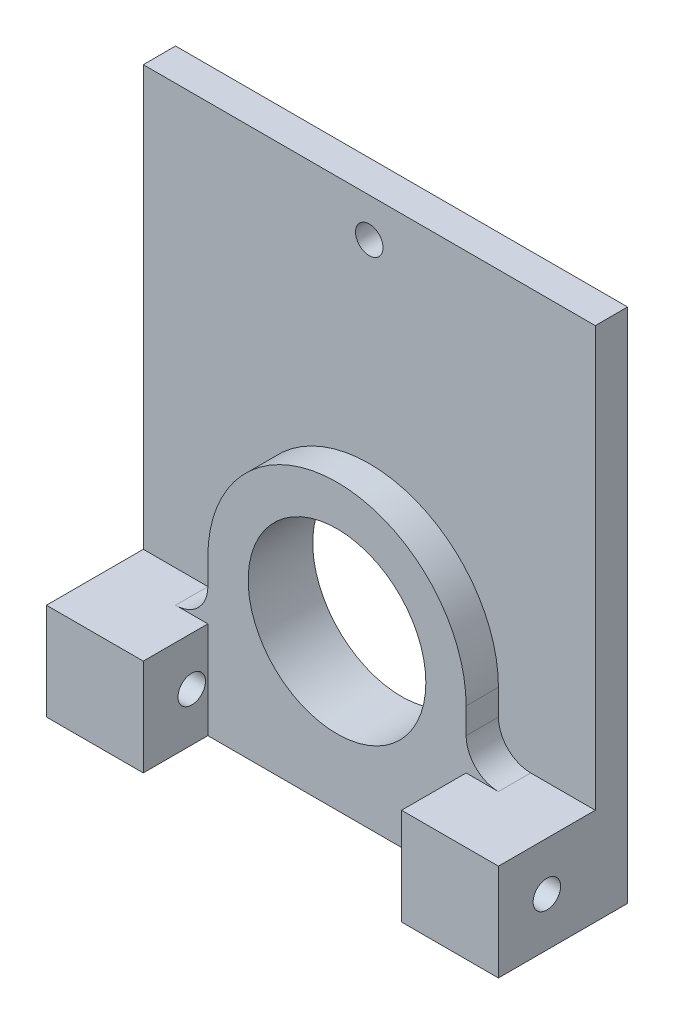
SolidWorks part; units mm, degrees
material "6061 Alloy"
ref_plane "Front Plane" through (0, 0, 0) normal (0, 0, 1) x (1, 0, 0)
ref_plane "Top Plane" through (0, 0, 0) normal (0, 1, 0) x (1, 0, 0)
ref_plane "Right Plane" through (0, 0, 0) normal (1, 0, 0) x (0, 0, -1)
sketch "Sketch1" plane through (0, 0, 0) normal (0, 0, 1) x (1, 0, 0)
  line L1 (-22.225, 25.4) -> (22.225, 25.4)
  line L2 (-22.225, 25.4) -> (-22.225, -25.4)
  line L3 (-22.225, -25.4) -> (22.225, -25.4)
  line L4 (22.225, 25.4) -> (22.225, -25.4)
  line L5 (-22.225, 25.4) -> (22.225, -25.4) construction
  line L6 (-22.225, -25.4) -> (22.225, 25.4) construction
  point P0 (0, 0)
  dimension "D1" = 44.45
  dimension "D2" = 50.8
extrude "Boss-Extrude1" add sketch "Sketch1" along normal blind 3.175
sketch "Sketch2" plane through (0, 0, 3.175) normal (0, 0, 1) x (1, 0, 0)
  line L0 (-12.7, -10.16) -> (-12.7, -25.4)
  line L1 (-22.225, -25.4) -> (22.225, -25.4) construction
  line L2 (12.7, -10.16) -> (12.7, -25.4)
  line L3 (-12.7, -25.4) -> (12.7, -25.4)
  arc A0 (12.7, -10.16) -> (-12.7, -10.16) centre (0, -10.16) ccw
  dimension "D1" = 25.4
  dimension "D2" = 15.24
extrude "Boss-Extrude2" add sketch "Sketch2" along normal blind 3.175
sketch "Sketch3" plane through (0, 0, 3.175) normal (0, 0, 1) x (1, 0, 0)
  line L0 (0, 0) -> (0, -25.4) construction
  line L1 (-22.225, -25.4) -> (-12.7, -25.4)
  line L2 (-22.225, -25.4) -> (-22.225, -15.875)
  line L3 (-22.225, -15.875) -> (-12.7, -15.875)
  line L4 (-12.7, -25.4) -> (-12.7, -15.875)
  line L5 (12.7, -25.4) -> (12.7, -15.875)
  line L6 (22.225, -15.875) -> (12.7, -15.875)
  line L7 (22.225, -25.4) -> (22.225, -15.875)
  line L8 (22.225, -25.4) -> (12.7, -25.4)
  line L9 (-12.7, -10.16) -> (-12.7, -25.4) construction
  dimension "D2" = 9.525
extrude "Boss-Extrude3" add sketch "Sketch3" along normal blind 9.525
sketch "Sketch4" plane through (0, 0, 6.35) normal (0, 0, 1) x (1, 0, 0)
  circle A0 centre (0, -10.16) radius 8.7376
  dimension "D1" = 17.4752
extrude "Cut-Extrude1" cut sketch "Sketch4" against normal through all
sketch "Sketch5" plane through (-22.225, 0, 0) normal (-1, 0, 0) x (0, 0, 1)
  line L0 (3.175, -15.875) -> (12.7, -25.4) construction
sketch "Sketch6" plane through (22.225, 0, 0) normal (1, 0, 0) x (0, 0, -1)
  line L0 (-3.175, -15.875) -> (-12.7, -25.4) construction
sketch "Sketch10" plane through (0, 0, 3.175) normal (0, 0, 1) x (1, 0, 0)
  line L0 (0, 2.54) -> (0, 25.4) construction
  line L1 (22.225, 25.4) -> (-22.225, 25.4) construction
  arc A0 (12.7, -10.16) -> (-12.7, -10.16) centre (0, -10.16) ccw construction
  circle A1 centre (0, -10.16) radius 8.7376 construction
  point P7 (0, 21.59)
  dimension "D1" = 31.75
hole_wizard "#6-32 Tapped Hole1" positions "3DSketch1" profile "Sketch8" tap size "#6-32" standard "ANSI Inch" end condition up to next
sketch3d "3DSketch1"
  line L0 (22.225, -15.875, 3.175) -> (22.225, -25.4, 12.7) construction
  line L1 (-22.225, -15.875, 3.175) -> (-22.225, -25.4, 12.7) construction
  point P0 (22.225, -20.6375, 7.9375)
  point P4 (-22.225, -20.6375, 7.9375)
  point P10 (0, 21.59, 3.175)
sketch "Sketch8" plane through (22.225, -20.6375, 7.9375) normal (0, 1, 0) x (0, 0, -1)
  line L0 (0, 0) -> (0, 9.525)
  line L1 (0, 9.525) -> (1.3525, 9.525)
  line L2 (1.3525, 9.525) -> (1.3525, 0)
  line L5 (1.3525, 0) -> (0, 0)
  line L11 (0, -6.35) -> (0, 107.95) construction
  dimension "Thru Tap Drill Dia." = 2.7051
  dimension "Thru Tap Drill Depth" = 9.525
cosmetic thread "Hole Thread4" parameters "D2"=3.5052
cosmetic thread "Hole Thread5" parameters "D2"=3.5052
cosmetic thread "Hole Thread6" parameters "D2"=3.5052
sketch "Sketch11" plane through (0, 0, 3.175) normal (0, 0, 1) x (1, 0, 0)
  line L0 (22.225, -15.875) -> (12.7, -15.875) construction
  line L1 (12.7, -15.875) -> (12.7, -10.16) construction
  line L2 (-12.7, -10.16) -> (-12.7, -15.875) construction
  line L3 (-12.7, -15.875) -> (-22.225, -15.875) construction
  line L4 (15.875, -15.875) -> (12.7, -15.875)
  line L5 (12.7, -15.875) -> (12.7, -12.7)
  line L6 (-12.7, -12.7) -> (-12.7, -15.875)
  line L7 (-12.7, -15.875) -> (-15.875, -15.875)
  arc A0 (-12.7, -12.7) -> (-15.875, -15.875) centre (-15.875, -12.7) cw
  arc A1 (12.7, -12.7) -> (15.875, -15.875) centre (15.875, -12.7) ccw
  dimension "D1" = 3.175
  dimension "D2" = 3.175
extrude "Boss-Extrude4" add sketch "Sketch11" along normal up to surface (3.175 mm away) up to face at (8.7376, -10.16, 6.35)
equation "\"D2@Sketch11\"=\"D1@Sketch11\""
